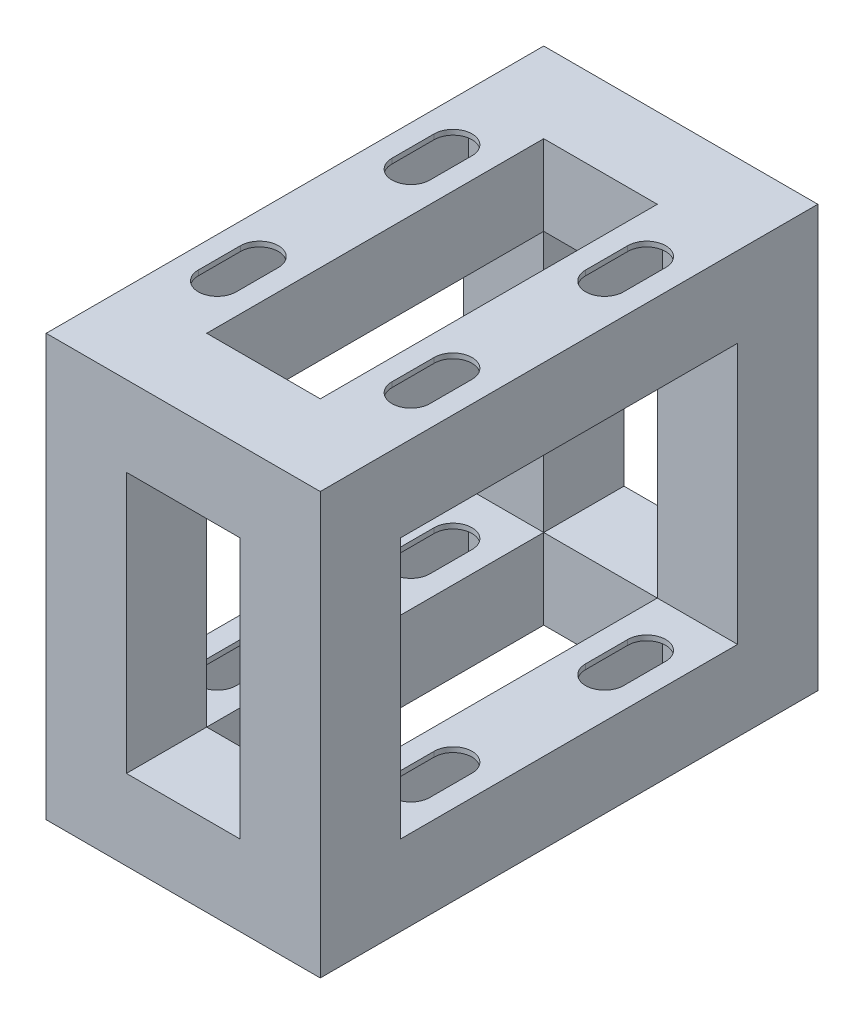
SolidWorks part; units mm, degrees
note: The reader was unsure of these and kept them because the rebuilt part matched: shared geometry of "Sketch1<3>".
ref_plane "Front Plane" through (0, 0, 0) normal (0, 0, 1) x (1, 0, 0)
ref_plane "Top Plane" through (0, 0, 0) normal (0, 1, 0) x (1, 0, 0)
ref_plane "Right Plane" through (0, 0, 0) normal (1, 0, 0) x (0, 0, -1)
sketch "Sketch1" plane through (0, 0, 0) normal (0, 1, 0) x (1, 0, 0)
  line L0 (-32.5, 0) -> (32.5, 0) construction
  line L1 (13.48, 40) -> (-13.48, 40)
  line L2 (13.48, 40) -> (13.48, -40)
  line L3 (13.48, -40) -> (-13.48, -40)
  line L4 (-13.48, 40) -> (-13.48, -40)
  line L5 (13.48, 40) -> (-13.48, -40) construction
  line L6 (13.48, -40) -> (-13.48, 40) construction
  line L7 (-22.981, 22.981) -> (22.981, -22.981) construction
  line L8 (-22.981, -22.981) -> (22.981, 22.981) construction
  line L9 (-22.981, 27.981) -> (-22.981, 17.981) construction
  line L10 (-18.481, 27.981) -> (-18.481, 17.981)
  line L11 (-27.481, 27.981) -> (-27.481, 17.981)
  line L12 (-22.981, -17.981) -> (-22.981, -27.981) construction
  line L13 (-18.481, -17.981) -> (-18.481, -27.981)
  line L14 (-27.481, -17.981) -> (-27.481, -27.981)
  line L15 (22.981, 27.981) -> (22.981, 17.981) construction
  line L16 (27.481, 27.981) -> (27.481, 17.981)
  line L17 (18.481, 27.981) -> (18.481, 17.981)
  line L18 (22.981, -27.981) -> (22.981, -17.981) construction
  line L19 (18.481, -27.981) -> (18.481, -17.981)
  line L20 (27.481, -27.981) -> (27.481, -17.981)
  circle A0 centre (0, 0) radius 32.5 construction
  arc A1 (-18.481, 27.981) -> (-27.481, 27.981) centre (-22.981, 27.981) ccw
  arc A2 (-27.481, 17.981) -> (-18.481, 17.981) centre (-22.981, 17.981) ccw
  arc A3 (-18.481, -17.981) -> (-27.481, -17.981) centre (-22.981, -17.981) ccw
  arc A4 (-27.481, -27.981) -> (-18.481, -27.981) centre (-22.981, -27.981) ccw
  arc A5 (27.481, 27.981) -> (18.481, 27.981) centre (22.981, 27.981) ccw
  arc A6 (18.481, 17.981) -> (27.481, 17.981) centre (22.981, 17.981) ccw
  arc A7 (18.481, -27.981) -> (27.481, -27.981) centre (22.981, -27.981) ccw
  arc A8 (27.481, -17.981) -> (18.481, -17.981) centre (22.981, -17.981) ccw
  point P0 (0, 0)
  point P16 (-22.981, 22.981)
  point P23 (-22.981, -22.981)
  point P30 (22.981, 22.981)
  point P37 (22.981, -22.981)
  point P42 (22.981, -22.981)
  dimension "D3" = 65
  dimension "D1" = 80
  dimension "D2" = 26.96
  dimension "D4" = 45
  dimension "D5" = 9
  dimension "D6" = 10
sketch "Sketch2" plane through (0, 0, 0) normal (0, 0, 1) x (1, 0, 0)
  line L1 (-32.53, -9.525) -> (-13.48, -9.525)
  line L2 (-32.53, -9.525) -> (-32.53, 9.525)
  line L3 (-32.53, 9.525) -> (-13.48, 9.525)
  line L4 (-13.48, -9.525) -> (-13.48, 9.525)
  line L5 (-32.53, -9.525) -> (-13.48, 9.525) construction
  line L6 (-32.53, 9.525) -> (-13.48, -9.525) construction
  line L7 (-14.68, 8.325) -> (-31.33, 8.325)
  line L8 (-14.68, 8.325) -> (-14.68, -8.325)
  line L9 (-14.68, -8.325) -> (-31.33, -8.325)
  line L10 (-31.33, 8.325) -> (-31.33, -8.325)
  line L11 (-14.68, 8.325) -> (-31.33, -8.325) construction
  line L12 (-14.68, -8.325) -> (-31.33, 8.325) construction
  point P0 (-23.005, 0)
  point P5 (-13.48, 0)
  point P6 (-23.005, 0)
  dimension "D1" = 19.05
  dimension "D2" = 1.2
sweep "Sweep1" add profiles "Sketch2" path "Sketch1"
extrude "Cut-Extrude1" cut sketch "Sketch1<3>" along normal up to surface (19.05 mm away) from surface
sketch "Sketch1<3>" plane through (0, 0, 0) normal (0, 1, 0) x (1, 0, 0) same geometry as "Sketch1"
ref_plane "Plane1" through (0, 0, 40) normal (0, 0, -1) x (-1, 0, 0)
sketch "Sketch3" plane through (0, 0, 40) normal (0, 0, -1) x (-1, 0, 0)
  line L0 (13.48, 9.525) -> (13.48, 40.475)
  line L1 (13.48, 9.525) -> (-13.48, 9.525)
  line L2 (-13.48, 40.475) -> (-13.48, 9.525)
  line L3 (13.48, 40.475) -> (-13.48, 40.475) construction
  line L4 (-32.53, -9.525) -> (32.53, -9.525) construction
  dimension "D1" = 50
sketch "Sketch4" plane through (0, 9.525, 0) normal (0, 1, 0) x (1, 0, 0)
  line L1 (-32.53, -59.05) -> (-13.48, -59.05)
  line L2 (-32.53, -59.05) -> (-32.53, -40)
  line L3 (-32.53, -40) -> (-13.48, -40)
  line L4 (-13.48, -59.05) -> (-13.48, -40)
  line L5 (-32.53, -59.05) -> (-13.48, -40) construction
  line L6 (-32.53, -40) -> (-13.48, -59.05) construction
  line L7 (-31.33, -57.85) -> (-14.68, -57.85)
  line L8 (-31.33, -57.85) -> (-31.33, -41.2)
  line L9 (-31.33, -41.2) -> (-14.68, -41.2)
  line L10 (-14.68, -57.85) -> (-14.68, -41.2)
  line L11 (-31.33, -57.85) -> (-14.68, -41.2) construction
  line L12 (-31.33, -41.2) -> (-14.68, -57.85) construction
  point P0 (-23.005, -49.525)
  point P5 (0, 0)
  point P6 (-23.005, -49.525)
sweep "Sweep2" add profiles "Sketch4" path "Sketch3"
ref_plane "Plane2" through (0, 0, 0) normal (0, 0, 1) x (1, 0, 0)
ref_plane "Plane3" through (0, 40.475, 0) normal (0, 1, 0) x (1, 0, 0)
mirror "Mirror1" about plane through (0, 0, 0) normal (0, 0, 1) of "Sweep2"
mirror "Mirror3" about plane through (0, 40.475, 0) normal (0, 1, 0) of bodies 104
